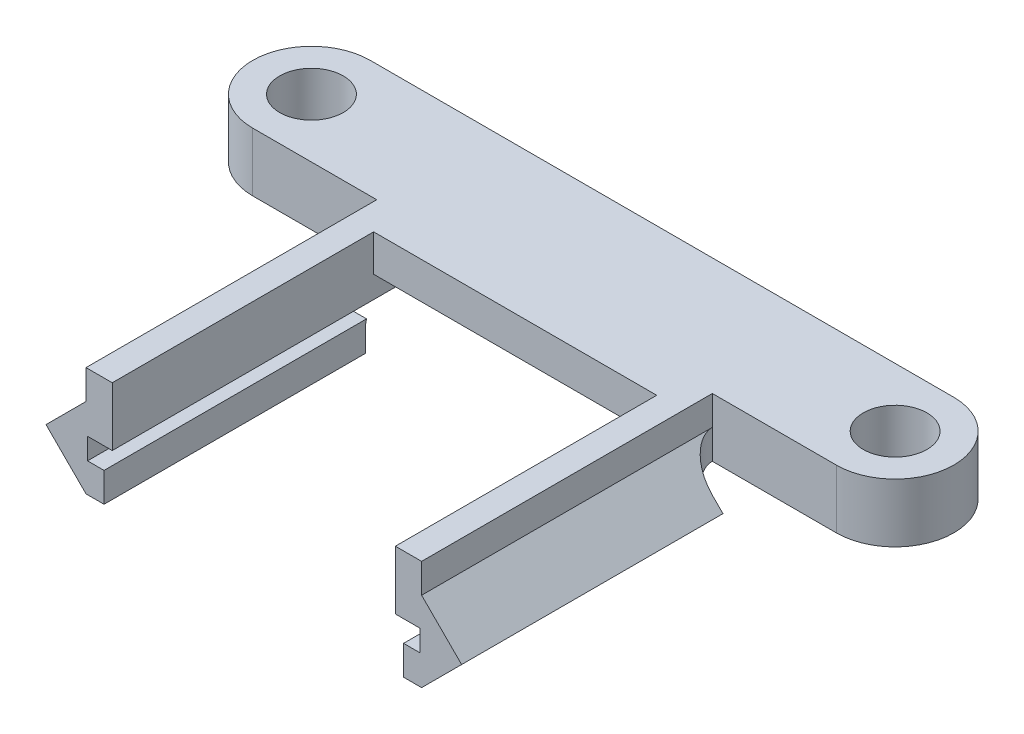
SolidWorks part; units mm, degrees
ref_plane "Front Plane" through (0, 0, 0) normal (0, 0, 1) x (1, 0, 0)
ref_plane "Top Plane" through (0, 0, 0) normal (0, 1, 0) x (1, 0, 0)
ref_plane "Right Plane" through (0, 0, 0) normal (1, 0, 0) x (0, 0, -1)
sketch "Sketch1" plane through (0, 0, 0) normal (0, 0, 1) x (1, 0, 0)
  line L0 (0.8255, 1.8415) -> (0, 1.8415)
  line L1 (0, 0) -> (0.8255, 0) construction
  line L2 (0, 0) -> (0, 1.8415) construction
  line L3 (0, 1.8415) -> (0.8255, 1.8415) construction
  line L4 (0.8255, 0) -> (0.8255, 1.8415) construction
  line L5 (0.4127, 1.8415) -> (0.4128, 0) construction
  line L6 (0, 0.9207) -> (0.8255, 0.9207) construction
  line L7 (0.8255, 0) -> (0, 0)
  line L8 (0, 0) -> (-0.9208, 0.9208) construction
  line L9 (-0.9208, 0.9208) -> (0, 1.8415) construction
  line L10 (26.0985, 0) -> (26.924, 0)
  line L11 (0.8255, 1.8415) -> (26.0985, 1.8415)
  line L12 (0.8255, 1.8415) -> (0.8255, 0) construction
  line L13 (0.8255, 0) -> (26.0985, 0)
  line L14 (26.0985, 1.8415) -> (26.0985, 0) construction
  line L15 (13.462, 0) -> (13.462, 1.8415) construction
  line L16 (0.8255, 0.9207) -> (26.0985, 0.9207) construction
  line L17 (26.924, 0) -> (27.8448, 0.9208) construction
  line L18 (26.0985, 1.8415) -> (26.924, 1.8415)
  line L19 (27.8448, 0.9208) -> (26.924, 1.8415) construction
  line L20 (-4.5129, 0.9207) -> (-1.0521, 4.3815)
  line L21 (0.8255, 4.3815) -> (-1.0521, 4.3815)
  line L22 (0.8255, 4.3815) -> (26.0985, 4.3815)
  line L23 (26.0985, 4.3815) -> (27.9761, 4.3815)
  line L24 (31.4369, 0.9207) -> (27.9761, 4.3815)
  line L25 (27.9761, -2.54) -> (31.4369, 0.9207)
  line L26 (26.0985, -2.54) -> (27.9761, -2.54)
  line L27 (0.8255, -2.54) -> (26.0985, -2.54)
  line L28 (0.8255, -2.54) -> (-1.0521, -2.54)
  line L29 (-1.0521, -2.54) -> (-4.5129, 0.9207)
  line L30 (0, 1.8415) -> (-0.9208, 1.8415)
  line L31 (-0.9208, 1.8415) -> (-0.9208, 0)
  line L32 (-0.9208, 0) -> (0, 0)
  line L33 (26.924, 1.8415) -> (27.8448, 1.8415)
  line L34 (27.8448, 1.8415) -> (27.8448, 0)
  line L35 (27.8448, 0) -> (26.924, 0)
  point P287 (13.462, 0.9207)
  point P500 (0.4127, 0.9207)
  dimension "D1" = 1.8415
  dimension "D2" = 0.8255
  dimension "D3" = 45
  dimension "D4" = 25.273
  dimension "D5" = 2.54
extrude "Boss-Extrude1" add sketch "Sketch1" along normal blind 22.606
sketch "Sketch2" plane through (0, 0, 22.606) normal (0, 0, 1) x (1, 0, 0)
  line L5 (13.462, 0) -> (13.462, -2.54) construction
  line L6 (-0.9208, 0) -> (27.8448, 0) construction
  line L7 (-1.0521, -2.54) -> (27.9761, -2.54) construction
  line L9 (0.508, 0) -> (26.416, 0)
  line L10 (0.508, 0) -> (0.508, -2.54)
  line L11 (0.508, -2.54) -> (26.416, -2.54)
  line L12 (26.416, 0) -> (26.416, -2.54)
  line L13 (13.462, -2.54) -> (13.462, 0) construction
  line L14 (0.508, -1.27) -> (26.416, -1.27) construction
  point P218 (13.462, -1.27)
  dimension "D1" = 0.508
extrude "Cut-Extrude1" cut sketch "Sketch2" against normal blind 22.606
sketch "Sketch5" plane through (0, 0, 0) normal (0, 0, -1) x (-1, 0, 0)
  line L12 (-31.4369, 0.9207) -> (-27.8448, 0.9208)
  line L13 (-27.8448, 0.9208) -> (-27.8448, 1.8415)
  line L14 (-27.8448, 1.8415) -> (0.9208, 1.8415)
  line L15 (0.9208, 1.8415) -> (0.9208, 0.9207)
  line L16 (0.9208, 1.8415) -> (0.9208, 0) construction
  line L17 (0.9208, 0.9207) -> (4.5129, 0.9207)
  line L18 (4.5129, 0.9207) -> (1.0521, 4.3815)
  line L19 (1.0521, 4.3815) -> (-27.9761, 4.3815)
  line L20 (-27.9761, 4.3815) -> (-31.4369, 0.9207)
extrude "Boss-Extrude2" add sketch "Sketch5" along normal blind 12.7
sketch "Sketch3" plane through (0, 4.3815, 0) normal (0, 1, 0) x (1, 0, 0)
  line L0 (13.462, 0) -> (13.462, -22.606) construction
  line L1 (27.9761, 0) -> (-1.0521, 0) construction
  line L2 (27.9761, -22.606) -> (-1.0521, -22.606) construction
  line L3 (6.1658, -15.0622) -> (3.048, -15.0622) construction
  line L4 (1.2192, 0) -> (25.7048, 0) construction
  line L5 (1.2192, 0) -> (1.2192, -22.606) construction
  line L6 (1.2192, -22.606) -> (25.7048, -22.606) construction
  line L7 (25.7048, 0) -> (25.7048, -22.606) construction
  line L8 (13.462, -22.606) -> (13.462, 0) construction
  line L9 (1.2192, -11.303) -> (25.7048, -11.303) construction
  line L10 (6.1658, 0) -> (20.7582, 0) construction
  line L11 (6.1658, 0) -> (6.1658, -15.0622) construction
  line L12 (6.1658, -15.0622) -> (20.7582, -15.0622) construction
  line L13 (20.7582, 0) -> (20.7582, -15.0622) construction
  line L14 (13.462, -15.0622) -> (13.462, 0) construction
  line L15 (6.1658, -7.5311) -> (20.7582, -7.5311) construction
  line L16 (3.048, 0) -> (23.876, 0) construction
  line L17 (3.048, 0) -> (3.048, -22.606) construction
  line L18 (3.048, -22.606) -> (23.876, -22.606) construction
  line L19 (23.876, 0) -> (23.876, -22.606) construction
  line L20 (13.462, -22.606) -> (13.462, 0) construction
  line L21 (3.048, -11.303) -> (23.876, -11.303) construction
  line L22 (3.048, -15.0622) -> (3.048, 0) construction
  line L23 (3.048, 0) -> (1.2192, 0)
  line L24 (1.2192, 0) -> (1.2192, -22.606)
  line L25 (1.2192, -22.606) -> (25.7048, -22.606)
  line L26 (25.7048, -22.606) -> (25.7048, 0)
  line L27 (25.7048, 0) -> (23.876, 0)
  line L28 (23.876, 0) -> (23.876, -15.0622) construction
  line L29 (23.876, -15.0622) -> (20.7582, -15.0622) construction
  line L32 (6.1658, 0) -> (20.7582, 0)
  line L33 (3.048, 0) -> (6.1658, 0)
  line L34 (20.7582, 0) -> (23.876, 0)
  point P250 (13.462, -11.303)
  point P383 (13.462, -7.5311)
  point P386 (13.462, -11.303)
  dimension "D1" = 24.4856
  dimension "D2" = 14.5923
  dimension "D3" = 15.0622
  dimension "D4" = 20.828
extrude "Cut-Extrude4" cut sketch "Sketch3" against normal up to vertex (2.54 mm away) up to point (-0.9208, 1.8415, 22.606)
sketch "Sketch6" plane through (0, 0, -12.7) normal (0, 0, -1) x (-1, 0, 0)
  line L2 (-27.9761, 4.3815) -> (-31.4369, 0.9207)
  line L3 (-31.4369, 0.9207) -> (-27.8448, 0.9208)
  line L4 (-27.8448, 0.9208) -> (-27.8448, 1.8415)
  line L5 (-27.8448, 1.8415) -> (-27.9761, 1.8415)
  line L6 (-27.9761, 1.8415) -> (-27.9761, 4.3815)
  line L8 (-13.462, 4.3815) -> (-13.462, 1.8415) construction
  line L9 (-0.8255, 4.3815) -> (-26.0985, 4.3815) construction
  line L11 (1.0521, 1.8415) -> (1.0521, 4.3815)
  line L12 (0.9208, 1.8415) -> (1.0521, 1.8415)
  line L13 (0.9208, 0.9208) -> (0.9208, 1.8415)
  line L14 (4.5129, 0.9208) -> (0.9208, 0.9208)
  line L15 (1.0521, 4.3815) -> (4.5129, 0.9208)
extrude "Cut-Extrude5" cut sketch "Sketch6" against normal up to surface (12.7 mm away) up to face at (27.9891, -0.5397, 0)
fillet "Fillet1" radius 2.54 4 edges at (-0.9864, 1.8415, 0) (-1.0521, 3.1115, 0) (27.9104, 1.8415, 0) (27.9761, 3.1115, 0)
sketch "Sketch7" plane through (0, 1.8415, 0) normal (0, -1, 0) x (1, 0, 0)
  line L2 (13.462, 0) -> (13.462, -12.7) construction
  line L3 (25.7048, 0) -> (1.2192, 0) construction
  line L4 (27.9761, -12.7) -> (-1.0521, -12.7) construction
  line L5 (-1.0521, -7.62) -> (27.9761, -7.62) construction
  line L6 (-1.0521, -2.54) -> (-1.0521, -12.7) construction
  line L7 (27.9761, -2.54) -> (27.9761, -12.7) construction
  line L8 (-1.0521, -7.62) -> (-11.778, -7.62) construction
  line L9 (-1.0521, -2.54) -> (-11.778, -2.54)
  line L10 (-1.0521, -2.54) -> (27.9761, -2.54)
  line L11 (27.9761, -2.54) -> (38.702, -2.54)
  line L12 (27.9761, -12.7) -> (38.702, -12.7)
  line L13 (-1.0521, -12.7) -> (27.9761, -12.7)
  line L14 (-1.0521, -12.7) -> (-11.778, -12.7)
  line L15 (-11.778, -2.54) -> (-11.778, -12.7) construction
  circle A4 centre (-11.778, -7.62) radius 2 construction
  circle A5 centre (38.702, -7.62) radius 2 construction
  arc A6 (-11.778, -12.7) -> (-11.778, -2.54) centre (-11.778, -7.62) cw
  arc A7 (38.702, -12.7) -> (38.702, -2.54) centre (38.702, -7.62) ccw
  dimension "D1" = 50.48
  dimension "D2" = 4
extrude "Boss-Extrude3" add sketch "Sketch7" against normal up to surface (2.54 mm away) up to face at (13.462, 4.3815, 5.9944)
hole_wizard "M5 Clearance Hole1" positions "Sketch8" profile "Sketch9" hole size "M5" standard "ANSI Metric" end condition through all
sketch "Sketch8" plane through (0, 1.8415, 0) normal (0, -1, 0) x (-1, 0, 0)
  point P6 (-38.702, 7.62)
  point P10 (11.778, 7.62)
sketch "Sketch9" plane through (38.702, 1.8415, -7.62) normal (1, 0, 0) x (0, 0, -1)
  line L0 (0, 0) -> (0, 2.54)
  line L1 (0, 2.54) -> (2.75, 2.54)
  line L2 (2.75, 2.54) -> (2.75, 0)
  line L5 (2.75, 0) -> (0, 0)
  line L11 (0, -6.35) -> (0, 107.95) construction
  dimension "Thru Hole Dia." = 5.5
  dimension "Thru Hole Depth" = 2.54
sketch "Sketch10" plane through (0, 0, -12.7) normal (0, 0, -1) x (-1, 0, 0)
  line L0 (-25.7048, 1.8415) -> (-25.7048, 4.3815) construction
  line L1 (-25.7048, 1.8415) -> (-1.2192, 1.8415)
  line L2 (-25.7048, 1.8415) -> (-25.7048, 3.7465)
  line L3 (-25.7048, 3.7465) -> (-1.2192, 3.7465)
  line L4 (-1.2192, 1.8415) -> (-1.2192, 3.7465)
  line L5 (-13.462, 3.7465) -> (-13.462, 1.8415) construction
  line L6 (-1.2192, 1.8415) -> (-1.2192, 4.3815) construction
  point P4 (0, 0)
  point P5 (0, 0)
  point P6 (0, 0)
  point P7 (0, 0)
  point P488 (-13.462, 2.4765)
  dimension "D1" = 1.905
extrude "Cut-Extrude8" cut sketch "Sketch10" against normal up to surface (12.7 mm away) up to face at (13.462, 3.1115, 0)
sketch "Sketch11" plane through (0, 4.3815, 0) normal (0, 1, 0) x (1, 0, 0)
  line L0 (-1.0521, 2.54) -> (-1.0521, -22.606)
  line L1 (-11.778, 12.7) -> (38.702, 12.7)
  line L2 (-11.778, 12.7) -> (-11.778, 2.54) construction
  line L3 (-11.778, 2.54) -> (-1.0521, 2.54)
  line L4 (38.702, 12.7) -> (38.702, 2.54) construction
  line L5 (13.462, 2.54) -> (13.462, 12.7) construction
  line L6 (-11.778, 7.62) -> (38.702, 7.62) construction
  line L7 (-1.0521, -22.606) -> (1.2192, -22.606)
  line L8 (1.2192, -22.606) -> (1.2192, 0)
  line L9 (1.2192, 0) -> (25.7048, 0)
  line L10 (25.7048, 0) -> (25.7048, -22.606)
  line L11 (25.7048, -22.606) -> (27.9761, -22.606)
  line L12 (27.9761, -22.606) -> (27.9761, 2.54)
  line L13 (27.9761, 2.54) -> (38.702, 2.54)
  arc A0 (-11.778, 2.54) -> (-11.778, 12.7) centre (-11.778, 7.62) cw
  arc A1 (38.702, 2.54) -> (38.702, 12.7) centre (38.702, 7.62) ccw
  circle A2 centre (-11.778, 7.62) radius 2.75
  circle A3 centre (-11.778, 7.62) radius 2.75 construction
  circle A4 centre (38.702, 7.62) radius 2.75
  point P132 (13.462, 7.62)
extrude "Boss-Extrude4" add sketch "Sketch11" along normal blind 2.54
